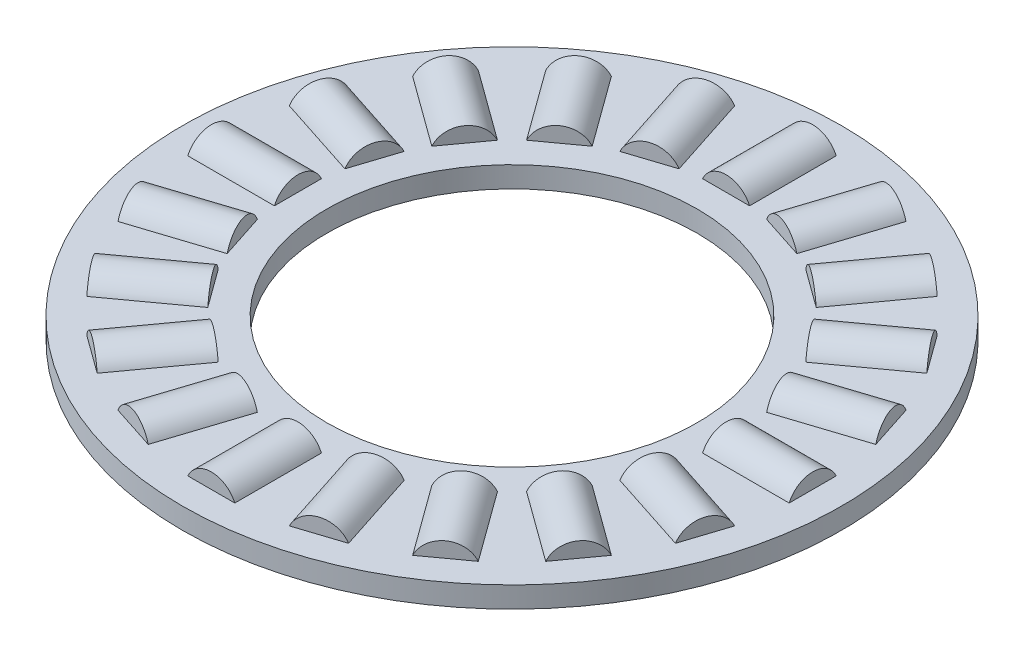
SolidWorks part; units mm, degrees
ref_plane "Front Plane" through (0, 0, 0) normal (0, 0, 1) x (1, 0, 0)
ref_plane "Top Plane" through (0, 0, 0) normal (0, 1, 0) x (1, 0, 0)
ref_plane "Right Plane" through (0, 0, 0) normal (1, 0, 0) x (0, 0, -1)
sketch "Sketch1" plane through (0, 0, 0) normal (1, 0, 0) x (0, 0, -1)
  line L0 (-12.7, 0) -> (12.7, 0) construction
  line L1 (0, -0.9922) -> (0, 0.9922) construction
  line L2 (-12.7, 0.405) -> (-7.1374, 0.405)
  line L3 (-12.7, 0.405) -> (-12.7, -0.405)
  line L4 (-12.7, -0.405) -> (-7.1374, -0.405)
  line L5 (-7.1374, 0.405) -> (-7.1374, -0.405)
  line L7 (-9.9187, 0.9922) -> (-9.9187, 0.405) construction
  line L8 (-11.5875, 0.9922) -> (-8.2499, 0.9922) construction
  line L9 (-11.5875, 0.9922) -> (-11.5875, -0.9922) construction
  line L10 (-11.5875, -0.9922) -> (-8.2499, -0.9922) construction
  line L11 (-8.2499, 0.9922) -> (-8.2499, -0.9922) construction
  line L12 (12.7, 0.9922) -> (12.7, -0.9922) construction
  point P16 (-11.5875, 0)
  point P21 (12.7, 0)
  dimension "OD" = 25.4
  dimension "ID" = 14.2748
  dimension "Washer Thickness" = 0.81
  dimension "D1" = 3.3376
  dimension "Thickness" = 1.9844
sketch "Sketch6" plane through (0, 0, 0) normal (0, 1, 0) x (1, 0, 0)
  circle A0 centre (0, 0) radius 12.7 construction
  circle A1 centre (0, 0) radius 7.1374 construction
  circle A2 centre (0, 0) radius 7.1438 construction
  dimension "For Shaft Diameter" = 14.2875
  dimension "OD" = 25.4
  dimension "ID" = 14.2748
sketch "Sketch5" plane through (0, 0, 0) normal (1, 0, 0) x (0, 0, -1)
  line L1 (-12.7, 0.405) -> (-7.1374, 0.405)
  line L2 (-12.7, 0.405) -> (-12.7, -0.405)
  line L3 (-12.7, -0.405) -> (-7.1374, -0.405)
  line L4 (-7.1374, 0.405) -> (-7.1374, -0.405)
revolve "Revolve3" add sketch "Sketch5" angle 360 about L1
sketch "Sketch3" plane through (0, 0, 0) normal (1, 0, 0) x (0, 0, -1)
  line L0 (-11.5875, 0.9922) -> (-11.5875, -0.9922) construction
  line L1 (-11.5875, 0) -> (-8.2499, 0)
  line L2 (-11.5875, 0) -> (-11.5875, 0.9922)
  line L3 (-11.5875, 0.9922) -> (-8.2499, 0.9922)
  line L4 (-8.2499, 0) -> (-8.2499, 0.9922)
revolve "Cut-Revolve1" cut sketch "Sketch3" angle 360 about L1
sketch "Sketch2" plane through (0, 0, 0) normal (1, 0, 0) x (0, 0, -1)
  line L1 (-11.5875, 0) -> (-8.2499, 0)
  line L2 (-11.5875, 0) -> (-11.5875, 0.9922)
  line L3 (-11.5875, 0.9922) -> (-8.2499, 0.9922)
  line L4 (-8.2499, 0) -> (-8.2499, 0.9922)
revolve "Revolve2" add sketch "Sketch2" angle 360 about L1
ref_axis "Axis1" through (0, 0.9922, 0) along (0, -1, 0)
pattern_circular "CirPattern1" count 20 every 18 about axis through (0, 0.9922, 0) along (0, -1, 0) of bodies 187 411
pattern_circular "CirPattern2" count 20 every 18 about axis through (0, 0.9922, 0) along (0, -1, 0) of "Cut-Revolve1"
equation "\"Rollers@CirPattern1\"= \"OD@Sketch1\" * 20"
equation "\"Angle@CirPattern1\" = 360/\"Rollers@CirPattern1\""
equation "\"D1@CirPattern2\" = \"Rollers@CirPattern1\""
equation "\"D2@CirPattern2\" = \"Angle@CirPattern1\""
equation "\"D1@Sketch1\"=((\"OD@Sketch1\"-\"ID@Sketch1\")/2)*.6"
